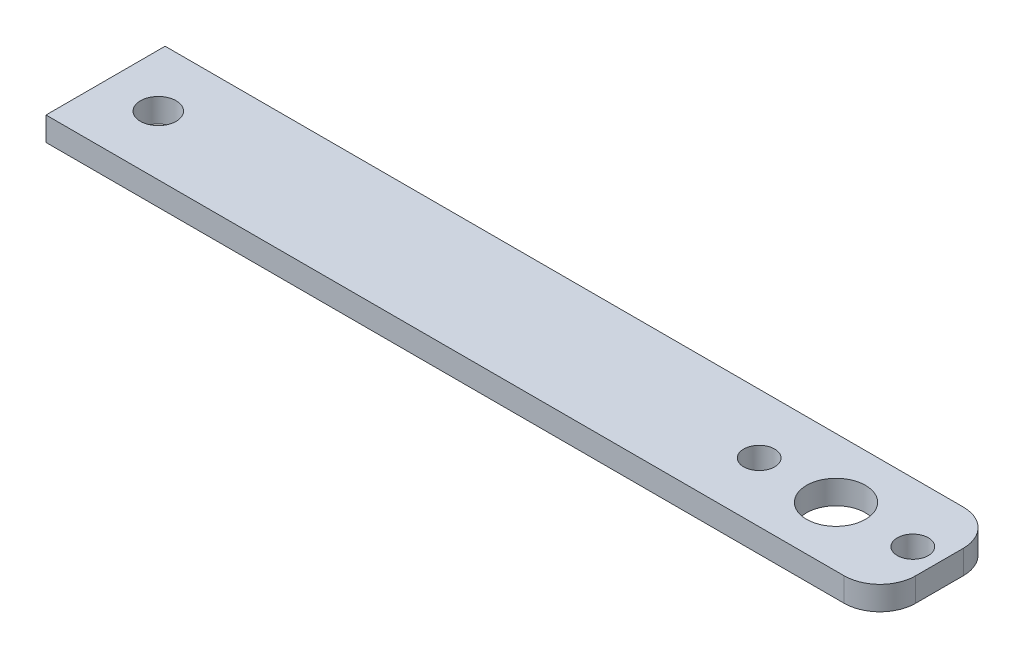
SolidWorks part; units mm, degrees
ref_plane "Front Plane" through (0, 0, 0) normal (0, 0, 1) x (1, 0, 0)
ref_plane "Top Plane" through (0, 0, 0) normal (0, 1, 0) x (1, 0, 0)
ref_plane "Right Plane" through (0, 0, 0) normal (1, 0, 0) x (0, 0, -1)
sketch "Sketch1" plane through (0, 0, 0) normal (0, 1, 0) x (1, 0, 0)
  line L1 (-35, 5) -> (35, 5)
  line L2 (-35, 5) -> (-35, -5)
  line L3 (-35, -5) -> (35, -5)
  line L4 (35, 5) -> (35, -5)
  line L5 (-35, 5) -> (35, -5) construction
  line L6 (-35, -5) -> (35, 5) construction
  point P0 (0, 0)
  dimension "D1" = 10
  dimension "D2" = 70
extrude "Boss-Extrude1" add sketch "Sketch1" along normal blind 2
sketch "Sketch2" plane through (0, 2, 0) normal (0, 1, 0) x (1, 0, 0)
  line L0 (26.3156, 5) -> (26.3156, -5) construction
  line L1 (-35, -5) -> (35, -5) construction
  line L2 (-29.219, -5) -> (-29.219, 5) construction
  circle A0 centre (26.3156, 0) radius 2.4729
  circle A1 centre (32.7656, 0) radius 1.3
  circle A3 centre (19.8656, 0) radius 1.3
  point P10 (26.3156, 0)
  point P14 (-29.219, 0)
  dimension "D1" = 2.6
  dimension "D2" = 6.45
extrude "Cut-Extrude1" cut sketch "Sketch2" against normal blind 3
fillet "Fillet1" radius 3 2 edges at (35, 1, 5) (35, 1, -5)
hole_wizard "Ø3.0mm Dowel Hole1" positions "Sketch3" profile "Sketch4" hole size "Ø3.0" standard "ISO" end condition through all
sketch "Sketch3" plane through (0, 2, 0) normal (0, 1, 0) x (1, 0, 0)
  point P0 (-30.5736, 0)
sketch "Sketch4" plane through (-30.5736, 2, 0) normal (1, 0, 0) x (0, 0, 1)
  line L0 (0, 0) -> (0, 2)
  line L1 (0, 2) -> (1.5, 2)
  line L2 (1.5, 2) -> (1.5, 0)
  line L5 (1.5, 0) -> (0, 0)
  line L11 (0, -6.35) -> (0, 107.95) construction
  dimension "Thru Hole Dia." = 3
  dimension "Thru Hole Depth" = 2
